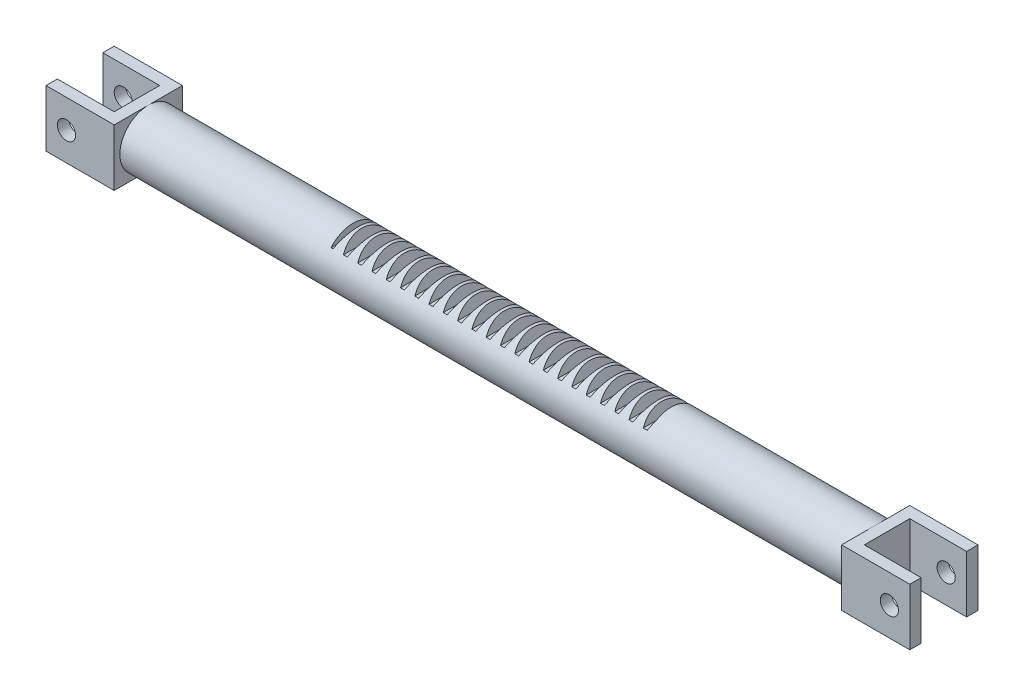
SolidWorks part; units mm, degrees
ref_plane "Front Plane" through (0, 0, 0) normal (0, 0, 1) x (1, 0, 0)
ref_plane "Top Plane" through (0, 0, 0) normal (0, 1, 0) x (1, 0, 0)
ref_plane "Right Plane" through (0, 0, 0) normal (1, 0, 0) x (0, 0, -1)
sketch "Sketch1" plane through (0, 0, 0) normal (0, 0, 1) x (1, 0, 0)
  line L186 (20.4391, 3.7836) -> (18.7153, 3.7836)
  line L187 (18.7153, 3.7836) -> (17.0774, 8.2836)
  line L188 (17.0774, 8.2836) -> (15.7937, 8.2836)
  line L189 (15.7937, 8.2836) -> (14.1559, 3.7836)
  line L190 (14.1559, 3.7836) -> (12.4321, 3.7836)
  line L191 (12.4321, 3.7836) -> (10.7943, 8.2836)
  line L192 (10.7943, 8.2836) -> (9.5105, 8.2836)
  line L193 (9.5105, 8.2836) -> (7.8727, 3.7836)
  line L194 (7.8727, 3.7836) -> (6.1489, 3.7836)
  line L195 (6.1489, 3.7836) -> (4.5111, 8.2836)
  line L196 (4.5111, 8.2836) -> (3.2274, 8.2836)
  line L197 (3.2274, 8.2836) -> (1.5895, 3.7836)
  line L198 (1.5895, 3.7836) -> (-0.1342, 3.7836)
  line L199 (-0.1342, 3.7836) -> (-1.7721, 8.2836)
  line L200 (-1.7721, 8.2836) -> (-3.0558, 8.2836)
  line L201 (-3.0558, 8.2836) -> (-4.6937, 3.7836)
  line L202 (-4.6937, 3.7836) -> (-6.4174, 3.7836)
  line L203 (-6.4174, 3.7836) -> (-8.0553, 8.2836)
  line L204 (-8.0553, 8.2836) -> (-9.339, 8.2836)
  line L205 (-9.339, 8.2836) -> (-10.9769, 3.7836)
  line L206 (-10.9769, 3.7836) -> (-12.7006, 3.7836)
  line L207 (-12.7006, 3.7836) -> (-14.3385, 8.2836)
  line L208 (-14.3385, 8.2836) -> (-15.6222, 8.2836)
  line L209 (-15.6222, 8.2836) -> (-17.2601, 3.7836)
  line L210 (-17.2601, 3.7836) -> (-18.9838, 3.7836)
  line L211 (-18.9838, 3.7836) -> (-20.6217, 8.2836)
  line L212 (-20.6217, 8.2836) -> (-21.9054, 8.2836)
  line L213 (-21.9054, 8.2836) -> (-23.5432, 3.7836)
  line L214 (-23.5432, 3.7836) -> (-25.267, 3.7836)
  line L215 (-25.267, 3.7836) -> (-26.9049, 8.2836)
  line L216 (-26.9049, 8.2836) -> (-28.1886, 8.2836)
  line L217 (-28.1886, 8.2836) -> (-29.8264, 3.7836)
  line L218 (-29.8264, 3.7836) -> (-31.5502, 3.7836)
  line L219 (-31.5502, 3.7836) -> (-33.188, 8.2836)
  line L220 (-33.188, 8.2836) -> (-34.4717, 8.2836)
  line L221 (-34.4717, 8.2836) -> (-36.1096, 3.7836)
  line L222 (-36.1096, 3.7836) -> (-37.8334, 3.7836)
  line L223 (-37.8334, 3.7836) -> (-39.4712, 8.2836)
  line L224 (-39.4712, 8.2836) -> (-40.7549, 8.2836)
  line L225 (-40.7549, 8.2836) -> (-42.3928, 3.7836)
  line L226 (-42.3928, 3.7836) -> (-44.1165, 3.7836)
  line L227 (-44.1165, 3.7836) -> (-45.7544, 8.2836)
  line L228 (-45.7544, 8.2836) -> (-47.0381, 8.2836)
  line L229 (-47.0381, 8.2836) -> (-48.676, 3.7836)
  line L230 (-48.676, 3.7836) -> (-50.3997, 3.7836)
  line L231 (-50.3997, 3.7836) -> (-52.0376, 8.2836)
  line L232 (-52.0376, 8.2836) -> (-53.3213, 8.2836)
  line L233 (-53.3213, 8.2836) -> (-54.9592, 3.7836)
  line L234 (-54.9592, 3.7836) -> (-56.6829, 3.7836)
  line L235 (-56.6829, 3.7836) -> (-58.3208, 8.2836)
  line L236 (-58.3208, 8.2836) -> (-59.6045, 8.2836)
  line L237 (-59.6045, 8.2836) -> (-61.2424, 3.7836)
  line L238 (-61.2424, 3.7836) -> (-62.9661, 3.7836)
  line L239 (-62.9661, 3.7836) -> (-64.604, 8.2836)
  line L240 (-64.604, 8.2836) -> (-65.8877, 8.2836)
  line L241 (-65.8877, 8.2836) -> (-67.5255, 3.7836)
  line L242 (-67.5255, 3.7836) -> (-69.2493, 3.7836)
  line L243 (-69.2493, 3.7836) -> (-70.8871, 8.2836)
  line L244 (-70.8871, 8.2836) -> (-72.1709, 8.2836)
  line L245 (-72.1709, 8.2836) -> (-73.8087, 3.7836)
  line L246 (-73.8087, 3.7836) -> (-75.5325, 3.7836)
  line L247 (-75.5325, 3.7836) -> (-77.1703, 8.2836)
  line L248 (-77.1703, 8.2836) -> (-78.454, 8.2836)
  line L249 (-78.454, 8.2836) -> (-80.0919, 3.7836)
  line L250 (-80.0919, 3.7836) -> (-81.8157, 3.7836)
  line L251 (-81.8157, 3.7836) -> (-83.4535, 8.2836)
  line L252 (-83.4535, 8.2836) -> (-84.7372, 8.2836)
  line L253 (-84.7372, 8.2836) -> (-86.3751, 3.7836)
  line L254 (-86.3751, 3.7836) -> (-88.0988, 3.7836)
  line L255 (-88.0988, 3.7836) -> (-89.7367, 8.2836)
  line L256 (-89.7367, 8.2836) -> (-91.0204, 8.2836)
  line L257 (-91.0204, 8.2836) -> (-92.6583, 3.7836)
  line L258 (-92.6583, 3.7836) -> (-94.382, 3.7836)
  line L259 (-94.382, 3.7836) -> (-96.0199, 8.2836)
  line L260 (-96.0199, 8.2836) -> (-97.3036, 8.2836)
  line L261 (-97.3036, 8.2836) -> (-98.9415, 3.7836)
  line L262 (-98.9415, 3.7836) -> (-100.6652, 3.7836)
  line L263 (-100.6652, 3.7836) -> (-102.3031, 8.2836)
  line L264 (-102.3031, 8.2836) -> (-103.5868, 8.2836)
  line L265 (-103.5868, 8.2836) -> (-105.2247, 3.7836)
  line L266 (-105.2247, 3.7836) -> (-106.9484, 3.7836)
  line L267 (-106.9484, 3.7836) -> (-108.5863, 8.2836)
  line L268 (-108.5863, 8.2836) -> (-109.87, 8.2836)
  line L269 (-109.87, 8.2836) -> (-111.5078, 3.7836)
  line L270 (-111.5078, 3.7836) -> (-113.2316, 3.7836)
  line L271 (-113.2316, 3.7836) -> (-114.8694, 8.2836)
  line L272 (-114.8694, 8.2836) -> (-116.1532, 8.2836)
  line L273 (-116.1532, 8.2836) -> (-117.791, 3.7836)
  line L274 (-117.791, 3.7836) -> (-118.6529, 3.7836)
  line L275 (-118.6529, 3.7836) -> (-118.6529, -23.7164)
  line L276 (-118.6529, -23.7164) -> (21.3471, -23.7164)
  line L277 (21.3471, -23.7164) -> (21.3471, 6.2784)
  line L278 (21.3471, 6.2784) -> (20.4391, 3.7836)
extrude "Boss-Extrude1" add sketch "Sketch1" along normal blind 30
sketch "Sketch2" plane through (-118.6529, 0, 0) normal (-1, 0, 0) x (0, 0, 1)
  line L0 (30, 8.2836) -> (0, 8.2836) construction
  line L1 (30, -23.7164) -> (0, -23.7164) construction
  circle A0 centre (15, -4.2164) radius 12.5
  circle A1 centre (15, -4.2164) radius 30
  point P7 (15, -23.7164)
  dimension "D1" = 25
  dimension "D2" = 60
extrude "Cut-Extrude1" cut sketch "Sketch2" against normal through all
sketch "Sketch3" plane through (-118.6529, 0, 0) normal (-1, 0, 0) x (0, 0, 1)
  circle A0 centre (15, -4.2164) radius 12.5
  arc A1 (5.3953, 3.7836) -> (24.6047, 3.7836) centre (15, -4.2164) ccw construction
extrude "Boss-Extrude2" add sketch "Sketch3" along normal blind 90
extrude "Boss-Extrude3" add sketch "Sketch3<2>" against normal blind 90 from offset 140 offset against normal yes
sketch "Sketch3<2>" plane through (-118.6529, 0, 0) normal (-1, 0, 0) x (0, 0, 1) same geometry as "Sketch3"
sketch "Sketch4" plane through (-208.6529, 0, 0) normal (-1, 0, 0) x (0, 0, 1)
  line L0 (0, 8.2836) -> (0, -16.7164)
  line L1 (0, 8.2836) -> (30, 8.2836)
  line L3 (0, -16.7164) -> (30, -16.7164)
  line L4 (30, 8.2836) -> (30, -16.7164)
  circle A0 centre (15, -4.2164) radius 12.5 construction
  circle A1 centre (15, -4.2164) radius 12.5 construction
  point P0 (15, -16.7164)
  dimension "D1" = 25
  dimension "D2" = 30
extrude "Boss-Extrude4" add sketch "Sketch4" along normal blind 5
ref_plane "Plane1" through (-48.6529, 0, 0) normal (1, 0, 0) x (0, 0, -1)
sketch "Sketch8" plane through (0, 8.2836, 0) normal (0, 1, 0) x (1, 0, 0)
  line L1 (-208.6529, 0) -> (-238.6529, 0)
  line L2 (-208.6529, 0) -> (-208.6529, -5)
  line L3 (-208.6529, -5) -> (-238.6529, -5)
  line L4 (-238.6529, 0) -> (-238.6529, -5)
  line L5 (-208.6529, -30) -> (-238.6529, -30)
  line L6 (-208.6529, -30) -> (-208.6529, -25)
  line L7 (-208.6529, -25) -> (-238.6529, -25)
  line L8 (-238.6529, -30) -> (-238.6529, -25)
  dimension "D1" = 5
  dimension "D2" = 30
  dimension "D3" = 5
extrude "Boss-Extrude7" add sketch "Sketch8" against normal blind 25
sketch "Sketch9" plane through (0, 0, 30) normal (0, 0, 1) x (1, 0, 0)
  line L0 (-238.6529, -16.7164) -> (-238.6529, 8.2836) construction
  circle A0 centre (-229.6529, -4.2164) radius 4
  point P4 (-238.6529, -4.2164)
  dimension "D1" = 8
  dimension "D2" = 9
extrude "Cut-Extrude2" cut sketch "Sketch9" against normal through all
mirror "Mirror1" about plane through (-48.6529, 0, 0) normal (1, 0, 0) of "Boss-Extrude4", "Cut-Extrude2", "Boss-Extrude7"
